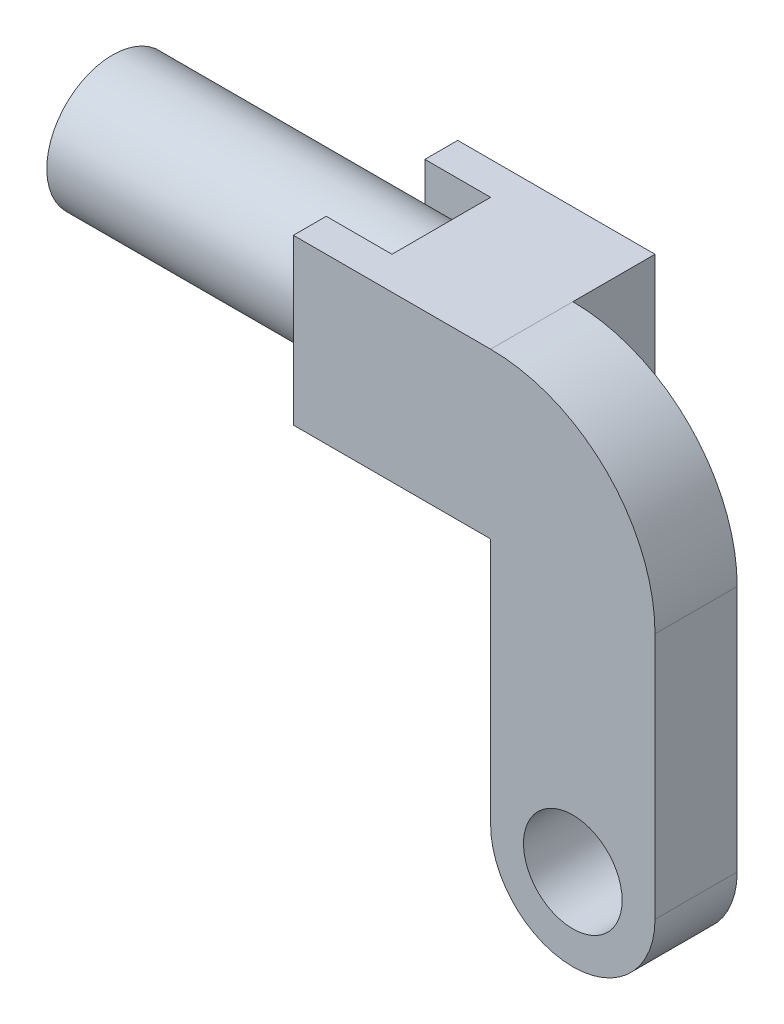
SolidWorks part; units mm, degrees
material "Ti-6Al-4VSolution treated and aged (SS)"
ref_plane "Front Plane" through (0, 0, 0) normal (0, 0, 1) x (1, 0, 0)
ref_plane "Top Plane" through (0, 0, 0) normal (0, 1, 0) x (1, 0, 0)
ref_plane "Right Plane" through (0, 0, 0) normal (1, 0, 0) x (0, 0, -1)
sketch "Sketch2" plane through (0, 0, 0) normal (1, 0, 0) x (0, 0, -1)
  circle A0 centre (0, 0) radius 12.7
  dimension "D1" = 25.4
extrude "Boss-Extrude1" add sketch "Sketch2" along normal blind 63.5
sketch "Sketch3" plane through (63.5, 0, 0) normal (1, 0, 0) x (0, 0, -1)
  line L1 (-15.875, 15.875) -> (15.875, 15.875)
  line L2 (-15.875, 15.875) -> (-15.875, -15.875)
  line L3 (-15.875, -15.875) -> (15.875, -15.875)
  line L4 (15.875, 15.875) -> (15.875, -15.875)
  line L5 (-15.875, 15.875) -> (15.875, -15.875) construction
  line L6 (-15.875, -15.875) -> (15.875, 15.875) construction
  point P0 (0, 0)
  dimension "D1" = 31.75
  dimension "D2" = 31.75
extrude "Boss-Extrude2" add sketch "Sketch3" along normal blind 25.4
sketch "Sketch6" plane through (0, 0, -15.875) normal (0, 0, -1) x (-1, 0, 0)
  line L1 (-63.5, 15.875) -> (-50.8, 15.875)
  line L2 (-63.5, 15.875) -> (-63.5, -15.875)
  line L3 (-63.5, -15.875) -> (-50.8, -15.875)
  line L4 (-50.8, 15.875) -> (-50.8, -15.875)
  dimension "D1" = 12.7
  dimension "D2" = 31.75
extrude "Boss-Extrude3" add sketch "Sketch6" against normal blind 6.35
mirror "Mirror1" about plane through (0, 0, 0) normal (0, 0, 1) of "Boss-Extrude3"
sketch "Sketch7" plane through (0, 0, 15.875) normal (0, 0, 1) x (1, 0, 0)
  line L0 (88.9, -15.875) -> (88.9, -63.627)
  line L1 (120.65, -63.627) -> (120.65, -15.875)
  line L2 (88.9, 15.875) -> (50.8, 15.875) construction
  circle A2 centre (104.775, -63.627) radius 15.875
  circle A3 centre (104.775, -63.627) radius 9.525
  circle A4 centre (88.9, -15.875) radius 31.75 construction
  arc A5 (88.9, 15.875) -> (120.65, -15.875) centre (88.9, -15.875) cw
  line M8 (88.9, -15.875) -> (88.9, 15.875)
  dimension "D1" = 19.05
  dimension "D2" = 47.752
extrude "Boss-Extrude4" add sketch "Sketch7" against normal blind 15.875 contours M8 | M8 | A2 | A3 region at (103.7812, -20.736, 15.875)
